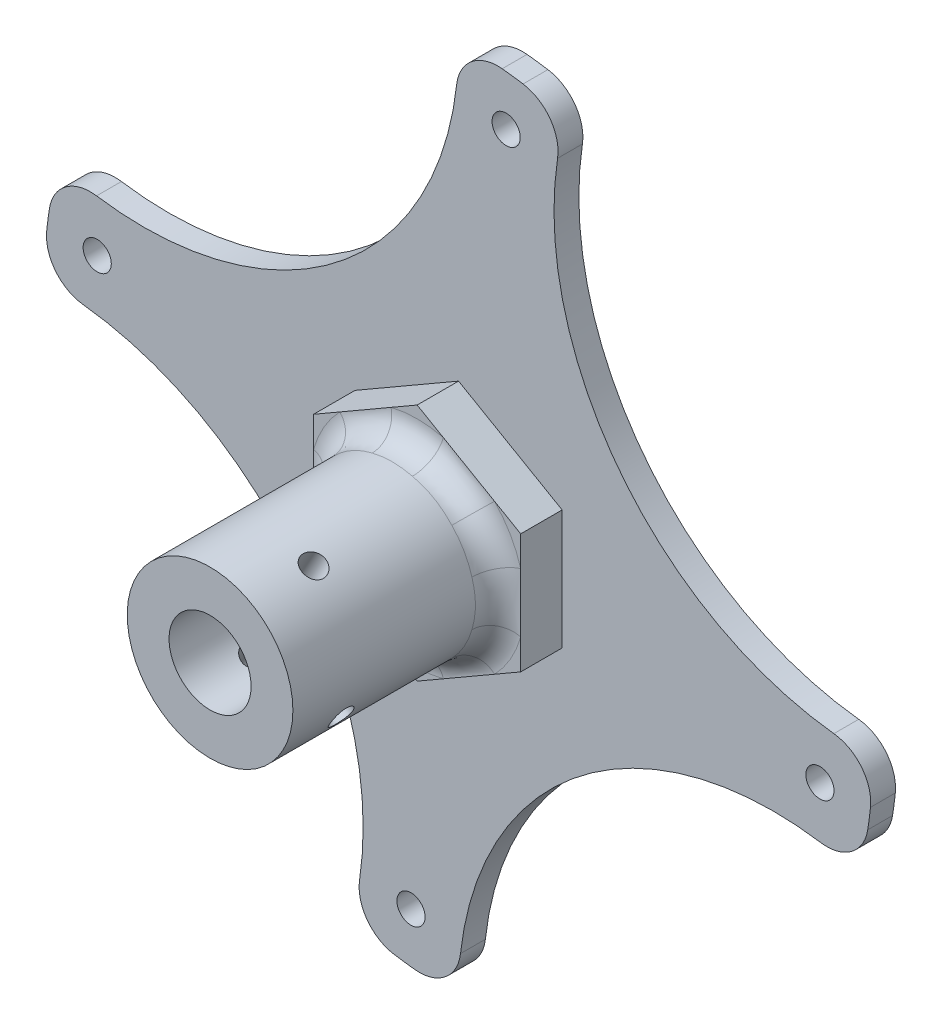
SolidWorks part; units mm, degrees
ref_plane "Front Plane" through (0, 0, 0) normal (0, 0, 1) x (1, 0, 0)
ref_plane "Top Plane" through (0, 0, 0) normal (0, 1, 0) x (1, 0, 0)
ref_plane "Right Plane" through (0, 0, 0) normal (1, 0, 0) x (0, 0, -1)
sketch "Sketch1" plane through (0, 0, 0) normal (0, 0, 1) x (1, 0, 0)
  circle A0 centre (0, 0) radius 50
  dimension "D1" = 100
extrude "Boss-Extrude1" add sketch "Sketch1" along normal blind 3
sketch "Sketch2" plane through (0, 0, 3) normal (0, 0, 1) x (1, 0, 0)
  line L1 (12.5, -7.2169) -> (12.5, 7.2169)
  line L2 (12.5, 7.2169) -> (0, 14.4338)
  line L3 (0, 14.4338) -> (-12.5, 7.2169)
  line L4 (-12.5, 7.2169) -> (-12.5, -7.2169)
  line L5 (-12.5, -7.2169) -> (0, -14.4338)
  line L6 (0, -14.4338) -> (12.5, -7.2169)
  circle A0 centre (0, 0) radius 12.5 construction
  dimension "D1" = 25
extrude "Boss-Extrude2" add sketch "Sketch2" along normal blind 5
sketch "Sketch3" plane through (0, 0, 8) normal (0, 0, 1) x (1, 0, 0)
  circle A0 centre (0, 0) radius 10
  dimension "D1" = 20
extrude "Boss-Extrude3" add sketch "Sketch3" along normal blind 25
fillet "Fillet1" radius 3 1 edges at (10, 0, 8)
sketch "Sketch4" plane through (0, 0, 33) normal (0, 0, 1) x (1, 0, 0)
  circle A0 centre (0, 0) radius 4.95
  dimension "D1" = 9.9
extrude "Cut-Extrude1" cut sketch "Sketch4" against normal through all
hole_wizard "Ø1.0mm Dowel Hole1" positions "3DSketch1" profile "Sketch5" hole size "Ø1.0" standard "ANSI Metric"
sketch3d "3DSketch1"
  point P0 (-8.696, 4.9375, 25.8574)
  point P2 (4.8442, 8.7483, 25.3286)
sketch "Sketch5" plane through (-8.696, 4.9375, 25.8574) normal (0, 0, 1) x (-0.4938, -0.8696, 0)
  line L0 (0, 0) -> (0, 34)
  line L1 (0, 34) -> (1.4, 33.1588)
  line L2 (1.4, 33.1588) -> (1.4, 0)
  line L5 (1.4, 0) -> (0, 0)
  line L10 (0, 34) -> (-1.4, 33.1588) construction
  line L11 (0, -6.35) -> (0, 107.95) construction
  dimension "Hole Dia." = 2.8
  dimension "Hole Depth" = 34
  dimension "Drill Angle" = 118
sketch "Sketch6" plane through (0, 0, 3) normal (0, 0, 1) x (1, 0, 0)
  line L0 (-50, 0) -> (0, 0)
  line L1 (0, 0) -> (-48.2963, 12.941)
  arc A0 (0, 50) -> (-48.2963, 12.941) centre (-37.997, 49.5186) cw
  circle A1 centre (0, 0) radius 50 construction
  arc A2 (-48.2963, 12.941) -> (0, 50) centre (0, 0) ccw
  arc A3 (50, 0) -> (12.941, 48.2963) centre (49.5186, 37.997) cw
  arc A4 (0, -50) -> (48.2963, -12.941) centre (37.997, -49.5186) cw
  arc A5 (-50, 0) -> (-12.941, -48.2963) centre (-49.5186, -37.997) cw
  point P9 (-48.2963, 12.941)
  point P10 (-48.2963, 12.941)
  point P11 (0, 0)
  point P21 (0, 0)
  circle M9 centre (0, 0) radius 50
  dimension "D1" = 38
  dimension "D3" = 4
  dimension "15" = 15
extrude "Cut-Extrude2" cut sketch "Sketch6" against normal blind 25 contours A0 L1 M9 | A3 A2 | A4 A2 | A5 L0 M9 region at (-29.8164, -22.879, 3) region at (-22.8789, 29.8165, 3) region at (22.879, -29.8164, 3) region at (29.8164, 22.879, 3)
fillet "Fillet2" radius 5 8 edges at (-48.2963, 12.941, 1.5) (-50, 0, 1.5) (-12.941, -48.2963, 1.5) (0, -50, 1.5) (48.2963, -12.941, 1.5) (50, 0, 1.5) (0, 50, 1.5) (12.941, 48.2963, 1.5)
sketch "Sketch7" plane through (0, 0, 0) normal (0, 0, -1) x (-1, 0, 0)
  line L0 (-6.5263, 49.5722) -> (0, 0) construction
  arc A0 (-5.2642, 49.7221) -> (-7.7842, 49.3903) centre (0, 0) ccw construction
  point P0 (-5.7432, 43.6236)
  point P10 (43.6236, 5.7432)
  point P11 (5.7432, -43.6236)
  point P12 (-43.6236, -5.7432)
  point P13 (0, 0)
  dimension "D1" = 6
  dimension "D2" = 4
hole_wizard "Ø1.0mm Dowel Hole2" positions "3DSketch2" profile "Sketch8" hole size "Ø1.0" standard "ANSI Metric"
sketch3d "3DSketch2"
  point P0 (5.7432, 43.6236, 0)
  point P3 (-43.6236, 5.7432, 0)
  point P6 (-5.7432, -43.6236, 0)
  point P9 (43.6236, -5.7432, 0)
sketch "Sketch8" plane through (5.7432, 43.6236, 0) normal (1, 0, 0) x (0, 1, 0)
  line L0 (0, 0) -> (0, 34)
  line L1 (0, 34) -> (1.7, 32.9785)
  line L2 (1.7, 32.9785) -> (1.7, 0)
  line L5 (1.7, 0) -> (0, 0)
  line L10 (0, 34) -> (-1.7, 32.9785) construction
  line L11 (0, -6.35) -> (0, 107.95) construction
  dimension "Hole Dia." = 3.4
  dimension "Hole Depth" = 34
  dimension "Drill Angle" = 118
